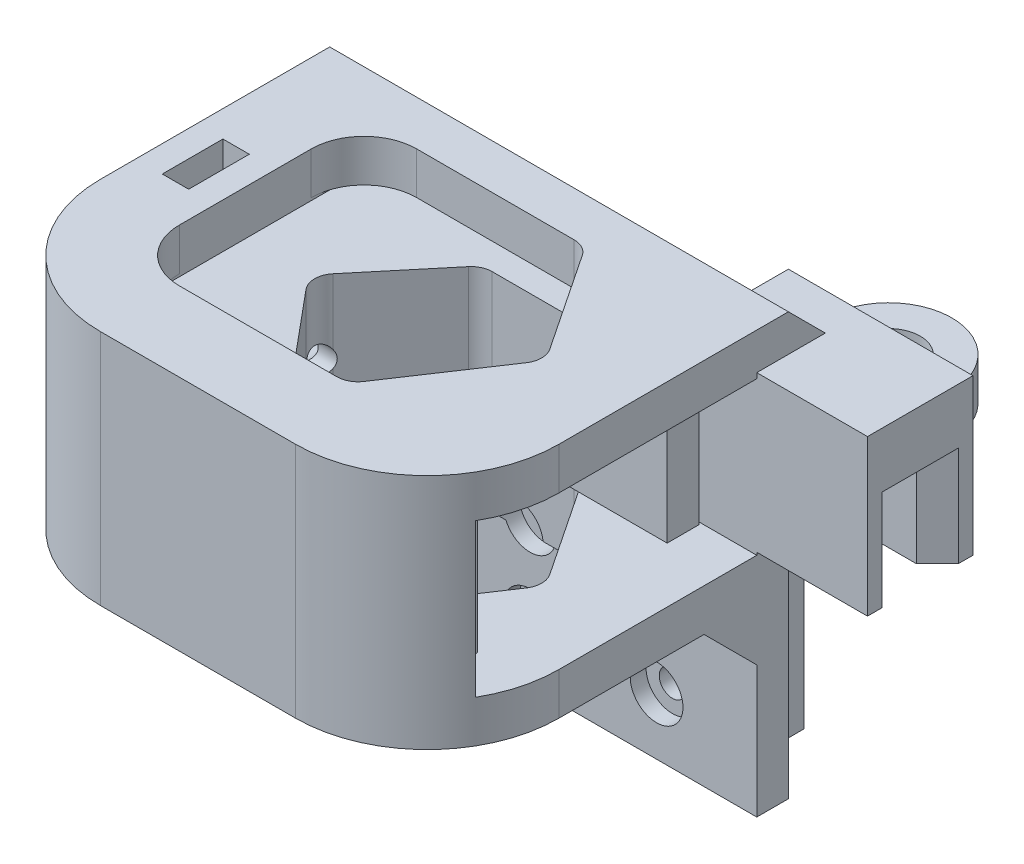
SolidWorks part; units mm, degrees
ref_plane "Спереди" through (0, 0, 0) normal (0, 0, 1) x (1, 0, 0)
ref_plane "Сверху" through (0, 0, 0) normal (0, 1, 0) x (1, 0, 0)
ref_plane "Справа" through (0, 0, 0) normal (1, 0, 0) x (0, 0, -1)
sketch "Эскиз1" plane through (0, 0, 0) normal (0, 0, 1) x (1, 0, 0)
  line L0 (-6, -14.5) -> (6, -14.5) construction
  line L1 (-10.5, -20) -> (10.5, -20)
  line L2 (-10.5, -20) -> (-10.5, 20)
  line L3 (-10.5, 20) -> (10.5, 20)
  line L4 (10.5, -20) -> (10.5, 20)
  line L5 (-10.5, -20) -> (10.5, 20) construction
  line L6 (-10.5, 20) -> (10.5, -20) construction
  line L8 (-10.5, 20) -> (-28, 20)
  line L9 (-10.5, 20) -> (-10.5, -20)
  line L10 (-10.5, -20) -> (-28, -20)
  line L11 (-28, 20) -> (-28, -20)
  line L12 (10.5, 20) -> (15.5, 20)
  line L13 (10.5, 20) -> (10.5, -20)
  line L14 (10.5, -20) -> (15.5, -20)
  line L15 (15.5, 20) -> (15.5, -20)
  circle A0 centre (-6, -14.5) radius 1.25
  circle A1 centre (6, -14.5) radius 1.25
  circle A2 centre (-6, -6.5) radius 1.25
  circle A3 centre (6, -6.5) radius 1.25
  point P0 (0, 0)
  point P14 (0, -14.5)
  dimension "D3" = 2.5
  dimension "D4" = 12
  dimension "D1" = 40
  dimension "D2" = 21
  dimension "D5" = 8
  dimension "D6" = 5.5
  dimension "D7" = 17.5
  dimension "D8" = 5
extrude "Бобышка-Вытянуть1" add sketch "Эскиз1" along normal blind 3 contours L1 L4 L3 L2 | L8 L11 L10 L2 | L15 L12 L4 L14 region at (0, 0.2513, 0) region at (-19.25, 0, 0) region at (13, 0, 0)
sketch "Эскиз2" plane through (0, -20, 0) normal (0, -1, 0) x (1, 0, 0)
  line L0 (0, -55) -> (0, 55) construction
  line L1 (10.5, 0) -> (8.75, 0)
  line L2 (10.5, 0) -> (10.5, -6.5)
  line L3 (10.5, -6.5) -> (8.75, -6.5)
  line L4 (8.75, 0) -> (8.75, -6.5)
  line L5 (-8.75, 0) -> (-8.75, -6.5)
  line L6 (-10.5, -6.5) -> (-8.75, -6.5)
  line L7 (-10.5, 0) -> (-10.5, -6.5)
  line L8 (-10.5, 0) -> (-8.75, 0)
  line L10 (-28, 0) -> (15.5, 0) construction
  dimension "D1" = 1.75
  dimension "D2" = 6.5
  dimension "D3" = 17.5
extrude "Бобышка-Вытянуть2" add sketch "Эскиз2" against normal blind 21.75
sketch "Эскиз3" plane through (0, 0, 3) normal (0, 0, 1) x (1, 0, 0)
  circle A11 centre (6, -6.5) radius 2.5
  circle A12 centre (6, -6.5) radius 2.5
  circle A14 centre (-6, -6.5) radius 2.5
  circle A15 centre (-6, -6.5) radius 2.5
  circle A17 centre (-6, -14.5) radius 2.5
  circle A18 centre (-6, -14.5) radius 2.5
  circle A20 centre (6, -14.5) radius 2.5
  circle A21 centre (6, -14.5) radius 2.5
  dimension "D1" = 1.25
  dimension "D2" = 1.25
  dimension "D3" = 1.25
  dimension "D4" = 1.25
extrude "Вырез-Вытянуть1" cut sketch "Эскиз3" against normal blind 1.5
sketch "Эскиз4" plane through (0, 1.75, 0) normal (0, 1, 0) x (1, 0, 0)
  line L0 (5, 11.5314) -> (5, 0)
  line L1 (3.5, 5.6746) -> (3.5, 7.6) construction
  line L2 (-8.1, 0) -> (8.1, 0) construction
  line L3 (15.5, 15.5) -> (15.5, 0)
  line L4 (15.5, 0) -> (5, 0)
  line L5 (15.5, 0) -> (10.5, -3)
  line L6 (10.5, -3) -> (10.5, 0)
  line L7 (10.5, -3) -> (15.5, -3)
  line L8 (15.5, -3) -> (15.5, 0)
  line L9 (10.5, 6.5) -> (10.5, 0) construction
  line L10 (-28, -3) -> (15.5, -3) construction
  circle A0 centre (9.5, 15.5) radius 3
  circle A1 centre (9.5, 15.5) radius 6
  line M2 (10.5, 0) -> (10.5, 6.5)
  line M3 (10.5, 6.5) -> (8.75, 6.5)
  line M4 (8.75, 6.5) -> (8.75, 0)
  line M5 (8.75, 0) -> (10.5, 0)
  dimension "D1" = 6
  dimension "D3" = 1.5
  dimension "D2" = 3
extrude "Бобышка-Вытянуть3" add sketch "Эскиз4" along normal blind 4 contours A1 L0 L4 L3 M4 M3 M2 | A1 A0 | M5 M2 M3 M4 | L6 L5 L4 | L7 L8 L5 region at (10.5091, 1.75, -5.5496) region at (7.4387, 1.75, -20.9537) region at (9.625, 1.75, -3.25) region at (12.1667, 1.75, 1) region at (13.8333, 1.75, 2)
sketch "Эскиз11" plane through (0, 0, 3) normal (0, 0, 1) x (1, 0, 0)
  line L0 (-28, 20) -> (15.5, 20) construction
  line L1 (8.5, 1.75) -> (26, 1.75)
  line L2 (8.5, 1.75) -> (8.5, 16.5)
  line L3 (8.5, 16.5) -> (26, 16.5)
  line L4 (26, 1.75) -> (26, 16.5)
  dimension "D1" = 17.5
  dimension "D2" = 14.75
  dimension "D3" = 3.5
  dimension "D4" = 8.5
extrude "Бобышка-Вытянуть6" add sketch "Эскиз11" against normal blind 10
sketch "Эскиз12" plane through (26, 0, 0) normal (1, 0, 0) x (0, 0, -1)
  line L0 (7, 1.75) -> (-3, 1.75) construction
  line L1 (0.375, 1.75) -> (3.625, 1.75)
  line L2 (0.375, 1.75) -> (0.375, 11.25)
  line L3 (0.375, 11.25) -> (3.625, 11.25)
  line L4 (3.625, 1.75) -> (3.625, 11.25)
  line L5 (7, 16.5) -> (-3, 16.5) construction
  point P8 (2, 16.5)
  point P9 (2, 11.25)
  dimension "D1" = 5.25
  dimension "D2" = 3.25
extrude "Вырез-Вытянуть5" cut sketch "Эскиз12" against normal offset from surface (15.5 mm away) 2 up to face at (8.5, 11.125, -3.5)
chamfer "Фаска3" distance 3.5 angle 45 7 edges at (12, 5.75, -7) (8.5, 5.75, -3.5) (8.5, 11.125, 0) (12, 16.5, 0) (5, 3.75, 0) (6.75, 5.75, 0) (15.5, 3.75, -7)
chamfer "Фаска6" distance 2 angle 45 2 edges at (26, 6.5, -0.375) (26, 6.5, -3.625)
sketch "Эскиз13" plane through (0, 20, 0) normal (0, 1, 0) x (1, 0, 0)
  line L1 (0.5, -4.25) -> (8, -15.5)
  line L2 (-16.7708, -15.5) -> (5.7292, -15.5) construction
  line L3 (0.5, -26.75) -> (8, -15.5)
  line L4 (15.5, -4.25) -> (15.5, -26.75)
  line L5 (15.5, -26.75) -> (0.5, -26.75)
  line L6 (0.5, -4.25) -> (15.5, -4.25)
  line L7 (-28, -4.25) -> (15.5, -4.25)
  line L8 (15.5, -26.75) -> (-28, -26.75)
  line L9 (15.5, -26.75) -> (15.5, -34.25)
  line L10 (15.5, -34.25) -> (-28, -34.25)
  line L11 (-28, -26.75) -> (-28, -34.25)
  line L12 (-28, -26.75) -> (-20.5, -26.75)
  line L13 (-28, -26.75) -> (-28, -4.25)
  line L14 (-28, -4.25) -> (-20.5, -4.25)
  line L15 (-20.5, -26.75) -> (-20.5, -4.25)
  line L16 (-28, -4.25) -> (-28, -3)
  line L17 (-28, -3) -> (15.5, -3)
  line L18 (15.5, -4.25) -> (15.5, -3)
  circle A0 centre (-5.5208, -15.5) radius 11.25 construction
  arc A1 (-15.5, -34.25) -> (-28, -21.75) centre (-15.5, -21.75) cw
  arc A2 (-15.5, -26.75) -> (-20.5, -21.75) centre (-15.5, -21.75) cw
  arc A3 (-15.5, -4.25) -> (-20.5, -9.25) centre (-15.5, -9.25) ccw
  line M9 (-28, -3) -> (15.5, -3)
  dimension "D1" = 22.5
  dimension "D5" = 12.5
  dimension "D2" = 7.5
  dimension "D3" = 15
  dimension "D4" = 7.5
  dimension "D7" = 43.5
  dimension "D8" = 1.25
extrude "Бобышка-Вытянуть7" add sketch "Эскиз13" against normal blind 22.5 contours L5 L4 L1 L3 M9 | L8 L11 L10 L9 L5 | L8 L15 L13 M9 | L8 A2 L15 | A3 L15 M9 | L6 L18 L16 L7 M9 region at (9.6667, 20, 15.5) region at (-6.25, 20, 3.625) region at (-19.3832, 20, 5.3668) region at (-4.2154, 20, 30.3619) region at (-24.2148, 20, 15.3976) region at (-19.3832, 20, 25.6332)
fillet "Скругление1" radius 12.5 1 edges at (15.5, 8.75, 34.25)
fillet "Скругление2" radius 2 3 edges at (0.5, 8.75, 26.75) (8, 8.75, 15.5) (0.5, 8.75, 4.25)
sketch "Эскиз14" plane through (-28, 0, 0) normal (-1, 0, 0) x (0, 0, 1)
  line L0 (16.6094, 20) -> (14.3906, 20) construction
  line L1 (16.6094, 20) -> (14.3906, 20)
  line L2 (21.75, -2.5) -> (21.75, 20) construction
  line L3 (18.375, 10.4099) -> (15.5, 12.0698)
  line L4 (15.5, 12.0698) -> (12.625, 10.4099)
  line L5 (12.625, 10.4099) -> (12.625, 7.0901)
  line L6 (12.625, 7.0901) -> (15.5, 5.4302)
  line L7 (15.5, 5.4302) -> (18.375, 7.0901)
  line L8 (18.375, 7.0901) -> (18.375, 10.4099)
  line L9 (12.625, 10.4099) -> (12.625, 20)
  line L10 (21.75, 20) -> (0, 20) construction
  line L11 (12.625, 20) -> (18.375, 20)
  line L12 (18.375, 20) -> (18.375, 10.4099)
  circle A0 centre (15.5, 8.75) radius 2.875 construction
  point P13 (21.75, 8.75)
  point P18 (15.5, 20)
  line M9 (21.75, 20) -> (0, 20)
  dimension "D1" = 5.75
extrude "Вырез-Вытянуть6" cut sketch "Эскиз14" against normal blind 2.5 from offset 2.5 contours L7 L8 L3 L4 L5 L6 | L12 L9 L4 L3 M9 region at (-28, 15.6068, 15.5) region at (-28, 8.75, 15.5) offset against normal yes
sketch "Эскиз15" plane through (-28, 0, 0) normal (-1, 0, 0) x (0, 0, 1)
  circle A0 centre (15.5, 8.75) radius 1.5
  dimension "D1" = 3
extrude "Вырез-Вытянуть7" cut sketch "Эскиз15" against normal up to surface (7.5 mm away) up to face at (-20.5, 8.75, 15.5)
sketch "Эскиз16" plane through (-20.5, 0, 0) normal (1, 0, 0) x (0, 0, -1)
  line L0 (-3, -2.5) -> (-21.75, -2.5) construction
  line L5 (-26.75, -2.5) -> (-26.75, 20) construction
  line L6 (-28, 1.5) -> (-3, 1.5)
  line L7 (-28, 1.5) -> (-28, 16)
  line L8 (-28, 16) -> (-3, 16)
  line L9 (-3, 1.5) -> (-3, 16)
  line L10 (-28, 1.5) -> (-3, 16) construction
  line L11 (-28, 16) -> (-3, 1.5) construction
  circle A0 centre (-15.5, 8.75) radius 1.5 construction
  circle A1 centre (-15.5, 8.75) radius 1.5 construction
  dimension "D1" = 4
  dimension "D2" = 1.25
extrude "Вырез-Вытянуть8" cut sketch "Эскиз16" along normal through all
ref_plane "Плоскость1" through (0, 8.75, 0) normal (0, 1, 0) x (1, 0, 0)
sketch "Эскиз17" plane through (0, 8.75, 0) normal (0, 1, 0) x (1, 0, 0)
  line L0 (-7.032, -6.5) -> (-14.532, -15.5)
  line L1 (-20.5, -27.5) -> (10.5, -27.5)
  line L2 (-20.5, -27.5) -> (-20.5, -3.5)
  line L3 (-20.5, -3.5) -> (10.5, -3.5)
  line L5 (-14.532, -15.5) -> (-20.5, -15.5) construction
  line L6 (-7.032, -24.5) -> (-14.532, -15.5)
  line L7 (10.5, -6.5) -> (10.5, -3.5)
  line L10 (-20.5, -21.75) -> (-20.5, -9.25) construction
  line L11 (-20.5, -21.75) -> (-20.5, -9.25) construction
  line L12 (13.8253, -28) -> (-20.5, -28) construction
  line L13 (-7.032, -6.5) -> (10.5, -6.5)
  line L14 (10.5, -24.5) -> (10.5, -27.5)
  line L15 (-7.032, -24.5) -> (10.5, -24.5)
  line L17 (1.0937, -5.1406) -> (7.2604, -14.3906) construction
  line L18 (1.0937, -25.8594) -> (7.2604, -16.6094) construction
  line L19 (15.5, 0) -> (15.5, -21.75) construction
  line L20 (15.5, -3) -> (-20.5, -3) construction
  circle A0 centre (-2.8167, -15.5) radius 9 construction
  dimension "D4" = 18
  dimension "D1" = 0.5
  dimension "D2" = 7.5
  dimension "D3" = 0.5
  dimension "D5" = 5
extrude "Бобышка-Вытянуть8" add sketch "Эскиз17" along normal mid plane 14 separate body
fillet "Скругление3" radius 2 3 edges at (-7.032, 8.75, 24.5) (-14.532, 8.75, 15.5) (-7.032, 8.75, 6.5)
sketch "Эскиз19" plane through (0, 0, 3.5) normal (0, 0, -1) x (-1, 0, 0)
  line L0 (20.5, 15.75) -> (20.5, 1.75) construction
  circle A0 centre (16.5, 8.75) radius 3
  point P5 (20.5, 8.75)
  point P6 (19.5, 8.75)
  dimension "D1" = 6
  dimension "D2" = 1
extrude "Вырез-Вытянуть10" cut sketch "Эскиз19" against normal blind 2.5
sketch "Эскиз20" plane through (0, 0, 6) normal (0, 0, -1) x (-1, 0, 0)
  circle A0 centre (16.5, 8.75) radius 1.4
  dimension "D1" = 2.8
extrude "Вырез-Вытянуть11" cut sketch "Эскиз20" against normal through all
sketch "Эскиз18" plane through (-20.5, 0, 0) normal (-1, 0, 0) x (0, 0, 1)
  line L0 (3.5, 15.75) -> (27.5, 15.75) construction
  line L1 (27.5, 15.75) -> (27.5, 1.75) construction
  circle A0 centre (15.5, 8.75) radius 1.5
  point P5 (15.5, 15.75)
  point P8 (27.5, 8.75)
  dimension "D1" = 3
extrude "Вырез-Вытянуть9" cut sketch "Эскиз18" against normal through all
delete or keep bodies "Тело-Удалить/Сохранить 1" [suppressed] type delete bodies bodies 117
chamfer "Фаска7" distance 5 angle 45 1 edges at (-6.25, -2.5, 3)
chamfer "Фаска8" distance 2 angle 45 1 edges at (-10.5, -9.125, 0)
